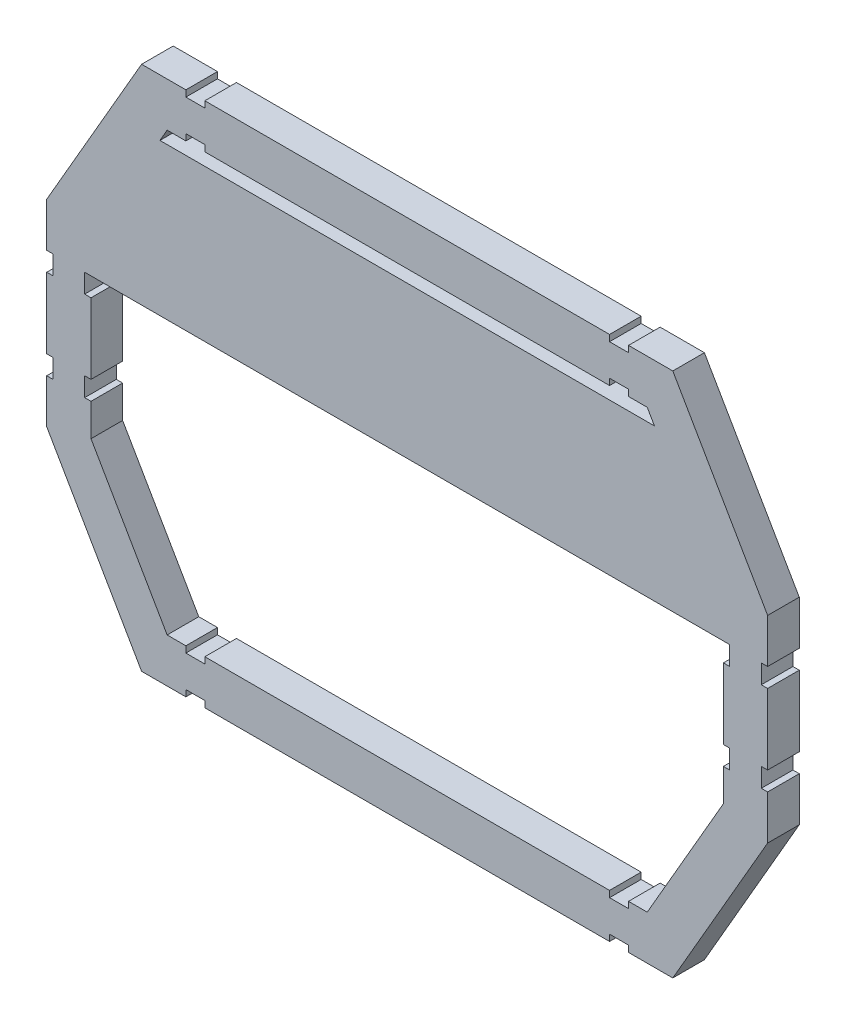
SolidWorks part; units mm, degrees
ref_plane "Plan de face" through (0, 0, 0) normal (0, 0, 1) x (1, 0, 0)
ref_plane "Plan de dessus" through (0, 0, 0) normal (0, 1, 0) x (1, 0, 0)
ref_plane "Plan de droite" through (0, 0, 0) normal (1, 0, 0) x (0, 0, -1)
sketch "Esquisse1" plane through (0, 0, 0) normal (0, 0, 1) x (1, 0, 0)
  line L0 (82.5398, -153.6268) -> (18.5398, -153.6268)
  line L1 (18.5398, -153.6268) -> (18.5398, -152.6268)
  line L2 (18.5398, -152.6268) -> (15.5398, -152.6268)
  line L3 (15.5398, -152.6268) -> (15.5398, -153.6268)
  line L4 (15.5398, -153.6268) -> (8.5398, -153.6268)
  line L5 (8.5398, -153.6268) -> (-6.4602, -127.646)
  line L6 (-6.4602, -127.646) -> (-6.4602, -120.646)
  line L7 (-6.4602, -120.646) -> (-5.4602, -120.646)
  line L8 (-5.4602, -120.646) -> (-5.4602, -117.646)
  line L9 (-5.4602, -117.646) -> (-6.4602, -117.646)
  line L10 (-6.4602, -117.646) -> (-6.4602, -106.4691)
  line L11 (50.5398, -153.6268) -> (50.5398, -70.4883) construction
  line L12 (100.5398, -112.0576) -> (0.5398, -112.0576) construction
  line L13 (1.0398, -140.6364) -> (50.5398, -112.0576) construction
  line L14 (0.5398, -106.4691) -> (0.5398, -117.646)
  line L15 (0.5398, -117.646) -> (-0.4602, -117.646)
  line L16 (-0.4602, -117.646) -> (-0.4602, -120.646)
  line L17 (-0.4602, -120.646) -> (0.5398, -120.646)
  line L18 (0.5398, -120.646) -> (0.5398, -125.7704)
  line L19 (0.5398, -125.7704) -> (12.5813, -146.6268)
  line L20 (12.5813, -146.6268) -> (15.5398, -146.6268)
  line L21 (15.5398, -146.6268) -> (15.5398, -147.6268)
  line L22 (15.5398, -147.6268) -> (18.5398, -147.6268)
  line L23 (18.5398, -147.6268) -> (18.5398, -146.6268)
  line L24 (18.5398, -146.6268) -> (82.5398, -146.6268)
  line L25 (1.0398, -83.4787) -> (50.5398, -112.0576) construction
  line L26 (18.5398, -77.4883) -> (82.5398, -77.4883)
  line L27 (18.5398, -76.4883) -> (18.5398, -77.4883)
  line L28 (15.5398, -76.4883) -> (18.5398, -76.4883)
  line L29 (15.5398, -77.4883) -> (15.5398, -76.4883)
  line L30 (12.5813, -77.4883) -> (15.5398, -77.4883)
  line L31 (88.4984, -77.4883) -> (89.642, -79.4691)
  line L33 (-0.4602, -103.4691) -> (0.5398, -103.4691)
  line L34 (-0.4602, -106.4691) -> (-0.4602, -103.4691)
  line L35 (0.5398, -106.4691) -> (-0.4602, -106.4691)
  line L36 (-5.4602, -106.4691) -> (-6.4602, -106.4691)
  line L37 (-5.4602, -103.4691) -> (-5.4602, -106.4691)
  line L38 (-6.4602, -103.4691) -> (-5.4602, -103.4691)
  line L39 (-6.4602, -96.4691) -> (-6.4602, -103.4691)
  line L40 (8.5398, -70.4883) -> (-6.4602, -96.4691)
  line L41 (15.5398, -70.4883) -> (8.5398, -70.4883)
  line L42 (15.5398, -71.4883) -> (15.5398, -70.4883)
  line L43 (18.5398, -71.4883) -> (15.5398, -71.4883)
  line L44 (18.5398, -70.4883) -> (18.5398, -71.4883)
  line L45 (82.5398, -70.4883) -> (18.5398, -70.4883)
  line L46 (100.0398, -83.4787) -> (50.5398, -112.0576) construction
  line L47 (100.0398, -140.6364) -> (50.5398, -112.0576) construction
  line L48 (82.5398, -70.4883) -> (82.5398, -71.4883)
  line L49 (82.5398, -71.4883) -> (85.5398, -71.4883)
  line L50 (85.5398, -71.4883) -> (85.5398, -70.4883)
  line L51 (85.5398, -70.4883) -> (92.5398, -70.4883)
  line L52 (92.5398, -70.4883) -> (107.5398, -96.4691)
  line L53 (107.5398, -96.4691) -> (107.5398, -103.4691)
  line L54 (107.5398, -103.4691) -> (106.5398, -103.4691)
  line L55 (106.5398, -103.4691) -> (106.5398, -106.4691)
  line L56 (106.5398, -106.4691) -> (107.5398, -106.4691)
  line L57 (100.5398, -106.4691) -> (101.5398, -106.4691)
  line L58 (101.5398, -106.4691) -> (101.5398, -103.4691)
  line L59 (101.5398, -103.4691) -> (100.5398, -103.4691)
  line L62 (88.4984, -77.4883) -> (85.5398, -77.4883)
  line L63 (85.5398, -77.4883) -> (85.5398, -76.4883)
  line L64 (85.5398, -76.4883) -> (82.5398, -76.4883)
  line L65 (82.5398, -76.4883) -> (82.5398, -77.4883)
  line L66 (82.5398, -147.6268) -> (82.5398, -146.6268)
  line L67 (85.5398, -147.6268) -> (82.5398, -147.6268)
  line L68 (85.5398, -146.6268) -> (85.5398, -147.6268)
  line L69 (88.4984, -146.6268) -> (85.5398, -146.6268)
  line L70 (100.5398, -125.7704) -> (88.4984, -146.6268)
  line L71 (100.5398, -120.646) -> (100.5398, -125.7704)
  line L72 (101.5398, -120.646) -> (100.5398, -120.646)
  line L73 (101.5398, -117.646) -> (101.5398, -120.646)
  line L74 (100.5398, -117.646) -> (101.5398, -117.646)
  line L75 (100.5398, -106.4691) -> (100.5398, -117.646)
  line L76 (107.5398, -117.646) -> (107.5398, -106.4691)
  line L77 (106.5398, -117.646) -> (107.5398, -117.646)
  line L78 (106.5398, -120.646) -> (106.5398, -117.646)
  line L79 (107.5398, -120.646) -> (106.5398, -120.646)
  line L80 (107.5398, -127.646) -> (107.5398, -120.646)
  line L81 (92.5398, -153.6268) -> (107.5398, -127.646)
  line L82 (85.5398, -153.6268) -> (92.5398, -153.6268)
  line L83 (85.5398, -152.6268) -> (85.5398, -153.6268)
  line L84 (82.5398, -152.6268) -> (85.5398, -152.6268)
  line L85 (82.5398, -153.6268) -> (82.5398, -152.6268)
  line L86 (0.5398, -103.4691) -> (100.5398, -103.4691)
  line L87 (11.4377, -79.4691) -> (89.642, -79.4691)
  line L88 (12.5813, -77.4883) -> (11.4377, -79.4691)
  point P10 (1.0398, -140.6364)
  point P41 (-6.4602, -112.0576)
  point P73 (50.5398, -77.4883)
  point P74 (50.5398, -146.6268)
  point P75 (50.5398, -146.6268)
  point P94 (107.5398, -112.0576)
  dimension "D1" = 1
  dimension "D2" = 3
  dimension "D3" = 7
  dimension "D4" = 3
  dimension "D5" = 7
  dimension "D6" = 60
  dimension "D7" = 90
  dimension "D8" = 1
  dimension "D9" = 1
  dimension "D10" = 1
  dimension "D11" = 7
  dimension "D12" = 7
  dimension "D13" = 7
  dimension "D14" = 30
  dimension "D15" = 35
  dimension "D16" = 24
extrude "Boss.-Extru.1" add sketch "Esquisse1" along normal blind 5
sketch "Esquisse2" plane through (0, 0, 5) normal (0, 0, 1) x (1, 0, 0)
  line L1 (25.951, -83.809) -> (75.951, -83.809)
  line L2 (25.951, -83.809) -> (25.951, -133.809)
  line L3 (25.951, -133.809) -> (75.951, -133.809)
  line L4 (75.951, -83.809) -> (75.951, -133.809)
  circle A0 centre (28.451, -86.309) radius 1.5
  circle A1 centre (73.451, -86.309) radius 1.5
  circle A2 centre (28.451, -131.309) radius 1.5
  circle A3 centre (73.451, -131.309) radius 1.5
  dimension "D1" = 2.5
  dimension "D2" = 2.5
  dimension "D5" = 50
  dimension "D6" = 50
  dimension "D3" = 2
  dimension "D4" = 2
